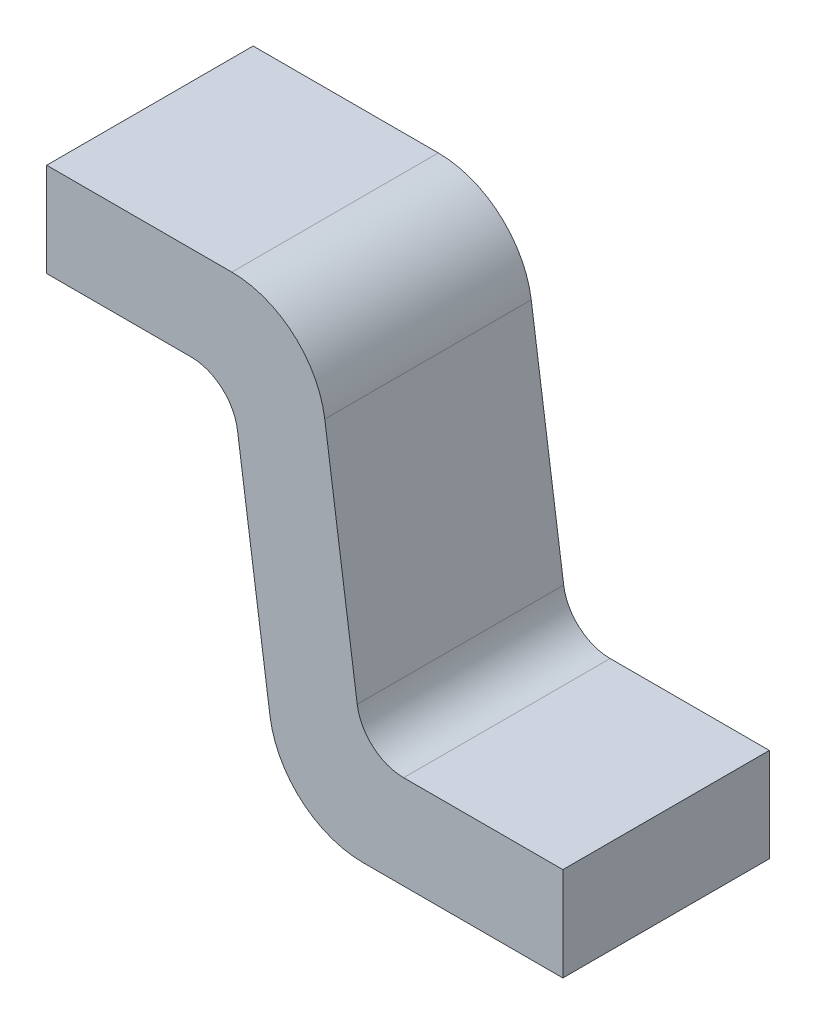
SolidWorks part; units mm, degrees
material "К270В2-II-08пс ГОСТ16523-97"
ref_plane "Спереди" through (0, 0, 0) normal (0, 0, 1) x (1, 0, 0)
ref_plane "Сверху" through (0, 0, 0) normal (0, 1, 0) x (1, 0, 0)
ref_plane "Справа" through (0, 0, 0) normal (1, 0, 0) x (0, 0, -1)
sketch "Эскиз1" plane through (0, 0, 0) normal (0, 0, 1) x (1, 0, 0)
  line L0 (0.6739, 0) -> (1.1, 0)
  line L1 (1.1, 0) -> (1.1, 0.2)
  line L2 (1.1, 0.2) -> (0.7608, 0.2)
  line L3 (0, 0.95) -> (0.3946, 0.95)
  line L4 (0, 0.95) -> (0, 0.75)
  line L5 (0.5926, 0.7778) -> (0.6618, 0.2861)
  line L6 (0, 0.85) -> (-0.3422, 0.85) construction
  line L7 (0.4758, 0.1722) -> (0.4067, 0.6639)
  line L8 (0.3077, 0.75) -> (0, 0.75)
  line L9 (0.6739, 0.2) -> (0.6739, 1.4959) construction
  line L10 (0, 0.75) -> (0, 0) construction
  line L11 (0.6739, 0) -> (0, 0) construction
  arc A0 (0.3946, 0.95) -> (0.5926, 0.7778) centre (0.3946, 0.75) cw
  arc A1 (0.4758, 0.1722) -> (0.6739, 0) centre (0.6739, 0.2) ccw
  arc A2 (0.7608, 0.2) -> (0.6618, 0.2861) centre (0.7608, 0.3) cw
  arc A3 (0.3077, 0.75) -> (0.4067, 0.6639) centre (0.3077, 0.65) cw
  point P16 (0.5, 0)
  dimension "D8" = 0.2
  dimension "D9" = 0.1
  dimension "D1" = 0.6
  dimension "D2" = 1.1
  dimension "D3" = 0.85
  dimension "D4" = 0.2
  dimension "D5" = 0.2
  dimension "D6" = 0.2
  dimension "D7" = 8
extrude "Бобышка-Вытянуть1" add sketch "Эскиз1" along normal blind 0.22 and the other way blind 0.22
